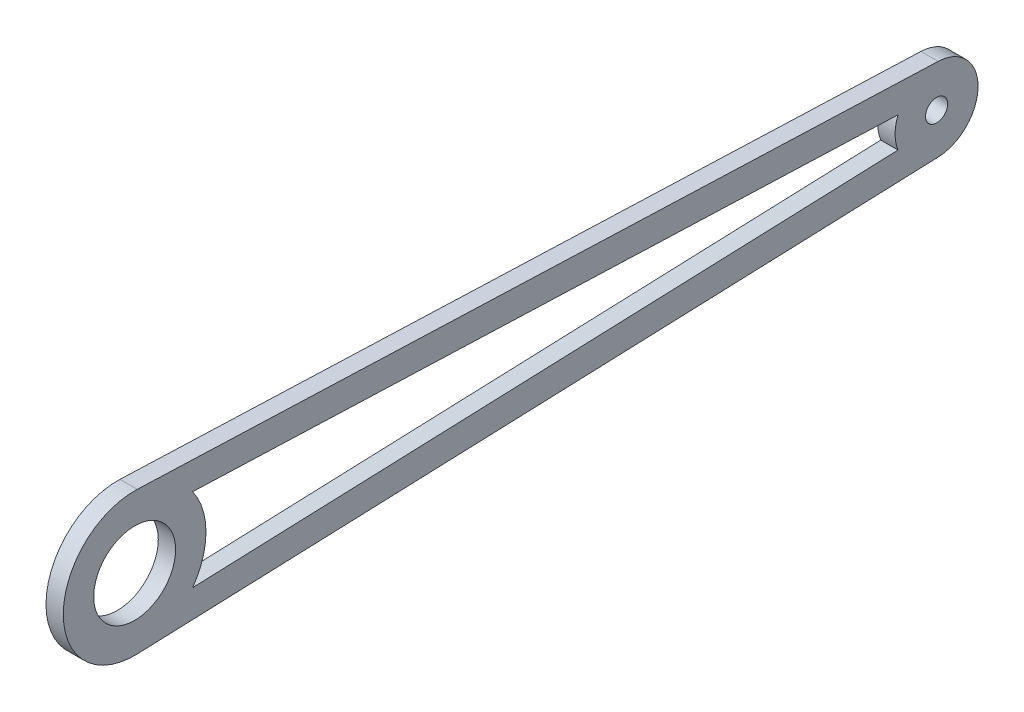
SolidWorks part; units mm, degrees
material "Delrin"
ref_plane "Front Plane" through (0, 0, 0) normal (0, 0, 1) x (1, 0, 0)
ref_plane "Top Plane" through (0, 0, 0) normal (0, 1, 0) x (1, 0, 0)
ref_plane "Right Plane" through (0, 0, 0) normal (1, 0, 0) x (0, 0, -1)
sketch "Sketch1" plane through (0, 0, 0) normal (1, 0, 0) x (0, 0, -1)
  line L0 (0.2441, 6.5487) -> (73.8019, 3.8074)
  line L1 (0, -6.5577) -> (73.8019, -3.8074)
  line L2 (-1000, 0) -> (49000, 0) construction
  line L3 (5.3265, 3.8175) -> (70.1177, 1.4029)
  line L4 (5.3265, -3.8175) -> (70.1177, -1.4029)
  line L5 (0.1495, 4.0104) -> (73.7073, 1.2691) construction
  line L6 (-0.0946, -4.0195) -> (73.7073, -1.2691) construction
  line L7 (73.66, -1000) -> (73.66, 49000) construction
  circle A0 centre (0, 0) radius 3.7592
  circle A1 centre (0, 0) radius 6.5532
  circle A2 centre (73.66, 0) radius 1.016
  circle A3 centre (73.66, 0) radius 3.81
  circle A4 centre (73.66, 15.875) radius 1.016
  circle A5 centre (73.66, 15.875) radius 3.556
  dimension "D1" = 7.5184
  dimension "D2" = 2.794
  dimension "D3" = 2.032
  dimension "D8" = 2.032
  dimension "D5" = 73.66
  dimension "D10" = 15.875
  dimension "D4" = 2.794
  dimension "D6" = 2.54
  dimension "D7" = 2.54
  dimension "D9" = 2.54
extrude "Boss-Extrude1" add sketch "Sketch1" along normal blind 1.5875 contours L2 A1 A0 | A1 L2 A0 | A1 L2 A3 L0 | L2 A1 L1 A3 | L2 A3 A2 | A3 L2 A2 region at (0, 3.9116, -37.468) region at (0, 5.6092, -3.0143) region at (0, 2.5687, -76.3262) region at (0, -3.9116, -37.468)
sketch3d "3DSketch1"
  line L0 (0, 6.5487, -0.2441) -> (0, 3.8074, -73.8019) construction
  line L1 (0, 3.8505, -72.644) -> (1.5875, 3.8505, -72.644)
  line L2 (0, 3.8505, -72.644) -> (0, -3.8505, -72.644)
  line L3 (0, -3.8505, -72.644) -> (1.5875, -3.8505, -72.644)
  line L4 (1.5875, 3.8505, -72.644) -> (1.5875, -3.8505, -72.644)
  line L5 (1.5875, -6.5487, -0.2441) -> (1.5875, -3.8074, -73.8019) construction
